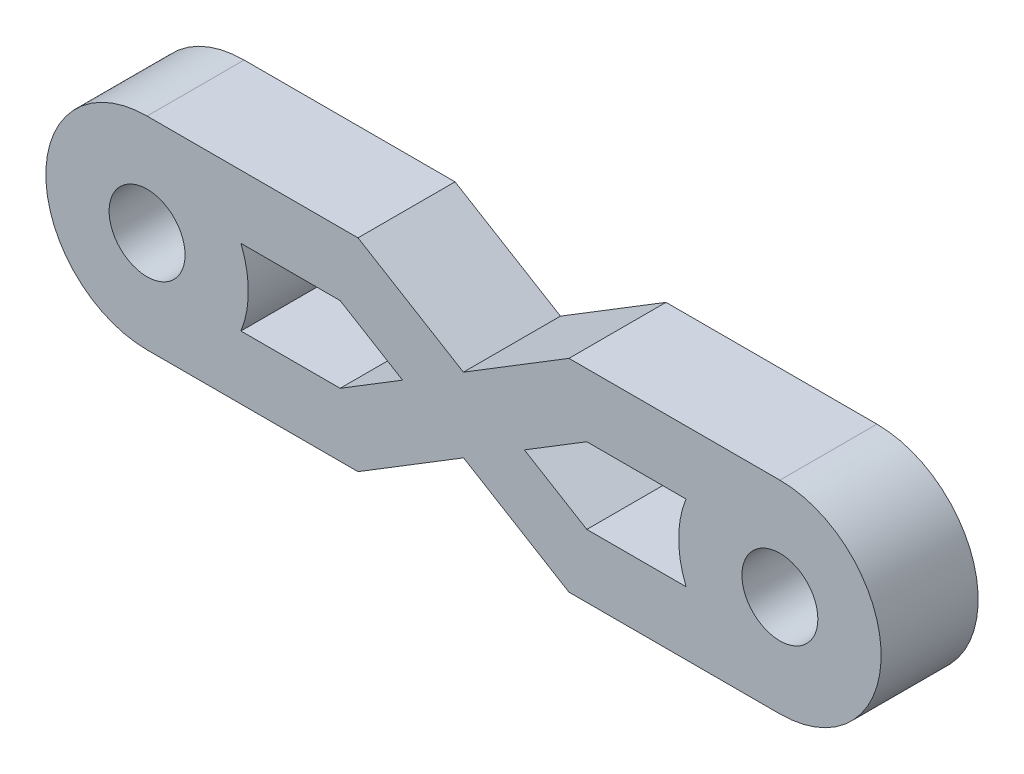
SolidWorks part; units mm, degrees
ref_plane "Front Plane" through (0, 0, 0) normal (0, 0, 1) x (1, 0, 0)
ref_plane "Top Plane" through (0, 0, 0) normal (0, 1, 0) x (1, 0, 0)
ref_plane "Right Plane" through (0, 0, 0) normal (1, 0, 0) x (0, 0, -1)
sketch "Sketch2" plane through (0, 0, 0) normal (0, 0, 1) x (1, 0, 0)
  line L0 (-117.2212, -4.8523) -> (-107.2212, -4.8523)
  line L1 (-87.2213, 4.8) -> (-97.2213, 4.8)
  line L2 (-97.2213, 4.8) -> (-102.2246, 1.7314)
  line L3 (-108.0679, -1.8523) -> (-112.7715, -1.8523)
  line L4 (-107.2212, -4.8523) -> (-102.2179, -1.7837)
  line L5 (-96.3746, 1.8) -> (-91.671, 1.8)
  line L6 (-87.2213, -4.8) -> (-97.2213, -4.8)
  line L7 (-97.2213, -4.8) -> (-102.2179, -1.7837)
  line L8 (-108.0679, 1.7477) -> (-112.7715, 1.7477)
  line L9 (-117.2212, 4.7477) -> (-107.2212, 4.7477)
  line L10 (-107.2212, 4.7477) -> (-102.2246, 1.7314)
  line L11 (-96.3746, -1.8) -> (-91.671, -1.8)
  line L12 (-99.3328, -0.0143) -> (-96.3746, 1.8)
  line L13 (-102.2179, -1.7837) -> (-99.3328, -0.0143) construction
  line L14 (-105.1097, -0.0381) -> (-108.0679, 1.7477)
  line L15 (-102.2179, -1.7837) -> (-105.1097, -0.0381) construction
  line L16 (-105.1097, -0.0381) -> (-108.0679, -1.8523)
  line L17 (-102.2246, 1.7314) -> (-105.1097, -0.0381) construction
  line L18 (-97.2213, -4.8) -> (-107.2212, -4.8523) construction
  line L19 (-99.3328, -0.0143) -> (-96.3746, -1.8)
  line L20 (-102.2246, 1.7314) -> (-99.3328, -0.0143) construction
  circle A0 centre (-117.2212, -0.0523) radius 1.8 construction
  circle A1 centre (-87.2213, 0) radius 1.8 construction
  circle A2 centre (-117.2212, -0.0523) radius 1.8
  circle A3 centre (-87.2213, 0) radius 1.8
  circle A4 centre (-117.2212, -0.0523) radius 4.8
  circle A5 centre (-87.2213, 0) radius 4.8
  circle M16 centre (-117.2212, -0.0523) radius 1.8
  circle M17 centre (-87.2213, 0) radius 1.8
  dimension "D1" = 3
  dimension "D2" = 3
  dimension "D3" = 3
  dimension "D4" = 3
extrude "Boss-Extrude1" add sketch "Sketch2" along normal up to surface (4.6 mm away) contours A4 M16 | A5 L1 L2 L10 L9 A4 L8 L14 L16 L3 L0 L4 L7 L6 L11 L19 L12 L5 | A5 M17 region at (-102.2213, -0.0262, 0) region at (-121.8855, -0.0523, 0) region at (-89.8287, -3.8674, 0)
